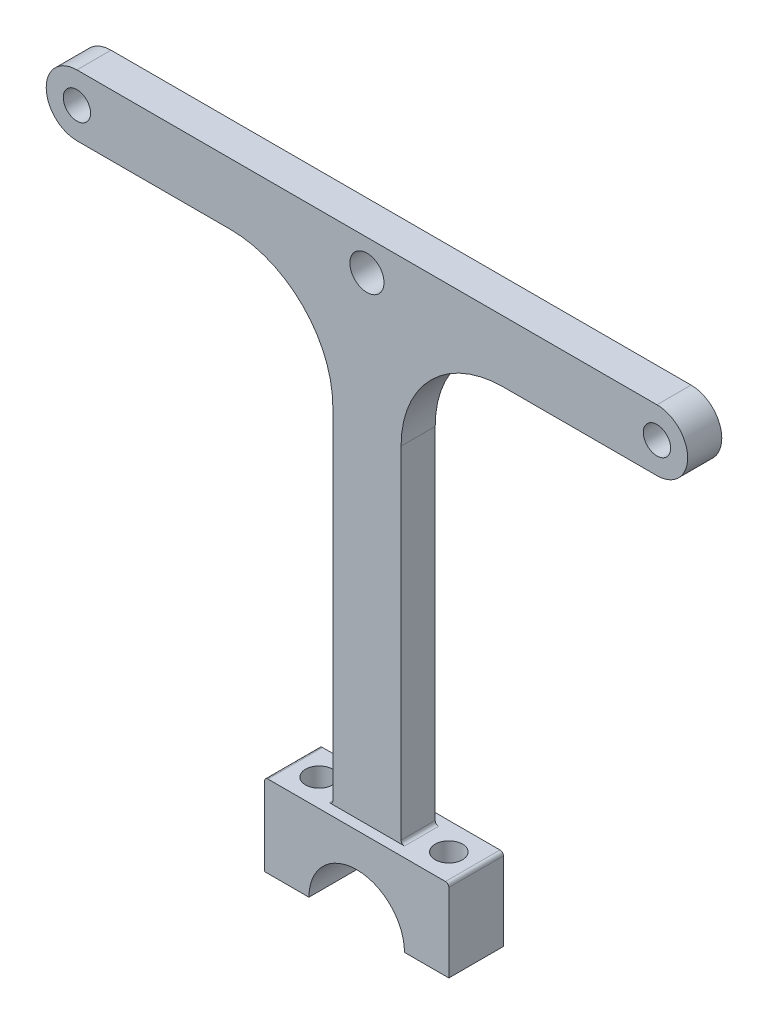
SolidWorks part; units mm, degrees
material "AISI 304"
ref_plane "Front Plane" through (0, 0, 0) normal (0, 0, 1) x (1, 0, 0)
ref_plane "Top Plane" through (0, 0, 0) normal (0, 1, 0) x (1, 0, 0)
ref_plane "Right Plane" through (0, 0, 0) normal (1, 0, 0) x (0, 0, -1)
sketch "Sketch1" plane through (0, 0, 0) normal (0, 0, 1) x (1, 0, 0)
  line L0 (0, 0) -> (0, 82)
  line L1 (0, 82) -> (42.5, 82)
  line L2 (0, 82) -> (-42.5, 82)
  line L3 (-42.5, 82) -> (42.5, 82) construction
  line L4 (-42.5, 86.5) -> (42.5, 86.5)
  line L5 (-42.5, 77.5) -> (42.5, 77.5)
  line L6 (0, 82) -> (5, 82)
  line L7 (0, 82) -> (-5, 82)
  line L8 (0, 0) -> (-13.5, 0)
  line L9 (5, 82) -> (-5, 82)
  line L10 (5, 82) -> (5, 0)
  line L11 (5, 0) -> (-5, 0)
  line L12 (-5, 82) -> (-5, 0)
  line L13 (0, 0) -> (13.5, 0)
  line L15 (13.5, 0) -> (-13.5, 0)
  line L16 (13.5, 0) -> (13.5, 12)
  line L17 (13.5, 12) -> (-13.5, 12)
  line L18 (-13.5, 0) -> (-13.5, 12)
  arc A0 (-42.5, 86.5) -> (-42.5, 77.5) centre (-42.5, 82) ccw
  arc A1 (42.5, 77.5) -> (42.5, 86.5) centre (42.5, 82) ccw
  circle A2 centre (-42.5, 82) radius 2
  circle A3 centre (0, 82) radius 2.5
  circle A4 centre (42.5, 82) radius 2
  circle A5 centre (0, 0) radius 7
  circle A6 centre (-20, 62.5) radius 15
  circle A7 centre (20, 62.5) radius 15
  point P5 (0, 82)
  dimension "D4" = 4.5
  dimension "D5" = 5
  dimension "D10" = 30
  dimension "D11" = 30
  dimension "D1" = 82
  dimension "D2" = 42.5
  dimension "D3" = 42.5
  dimension "D6" = 5
  dimension "D7" = 13.5
  dimension "D8" = 13.5
  dimension "D9" = 12
extrude "Boss-Extrude1" add sketch "Sketch1" along normal blind 5 contours A5 L15 L16 L17 L10 | A5 L10 L17 L0 | A5 L0 L17 L12 | A5 L12 L17 L18 L15 | L17 L0 L5 L12 | L17 L10 L5 L0 | A7 L5 L10 | A6 L12 L5 | A4 L10 L5 A1 L4 A0 L12 A2 L9 A3 | A3 L0 L5 L10 L9 | A3 L9 L12 L5 L0 region at (-2.6489, 9.1412, 0) region at (2.6489, 9.1412, 0) region at (-2.5, 44.75, 0) region at (2.5, 44.75, 0) region at (9.4935, 6.2919, 0) region at (-9.4935, 6.2919, 0) region at (-2.9015, 79.4182, 0) region at (2.9015, 79.4182, 0) region at (-8.3505, 74.1495, 0) region at (-12.5, 78.4443, 0) region at (8.3505, 74.1495, 0)
extrude "Boss-Extrude2" add sketch "Sketch1<3>" along normal blind 6.5 and the other way blind 1.5 contours A5 L15 L16 L17 L10 | A5 L12 L17 L18 L15 | A5 L0 L17 L12 | A5 L10 L17 L0 region at (-2.6489, 9.1412, 0) region at (2.6489, 9.1412, 0) region at (9.4935, 6.2919, 0) region at (-9.4935, 6.2919, 0)
sketch "Sketch1<3>" plane through (0, 0, 0) normal (0, 0, 1) x (1, 0, 0) same geometry as "Sketch1"
sketch "Sketch2" plane through (0, 12, 0) normal (0, 1, 0) x (1, 0, 0)
  line L0 (13.5, 1.5) -> (-13.5, 1.5) construction
  circle A0 centre (9.5, -2.5) radius 2
  circle A1 centre (-9.5, -2.5) radius 2
  point P6 (0, 1.5)
  point P8 (0.136, 3.6184)
  dimension "D1" = 4
  dimension "D2" = 4
  dimension "D3" = 19
  dimension "D4" = 9.5
extrude "Cut-Extrude1" cut sketch "Sketch2" against normal blind 100
fillet "Fillet1" radius 0.5 4 edges at (-13.5, 12, 2.5) (-5, 12, 2.5) (13.5, 12, 2.5) (5, 12, 2.5)
